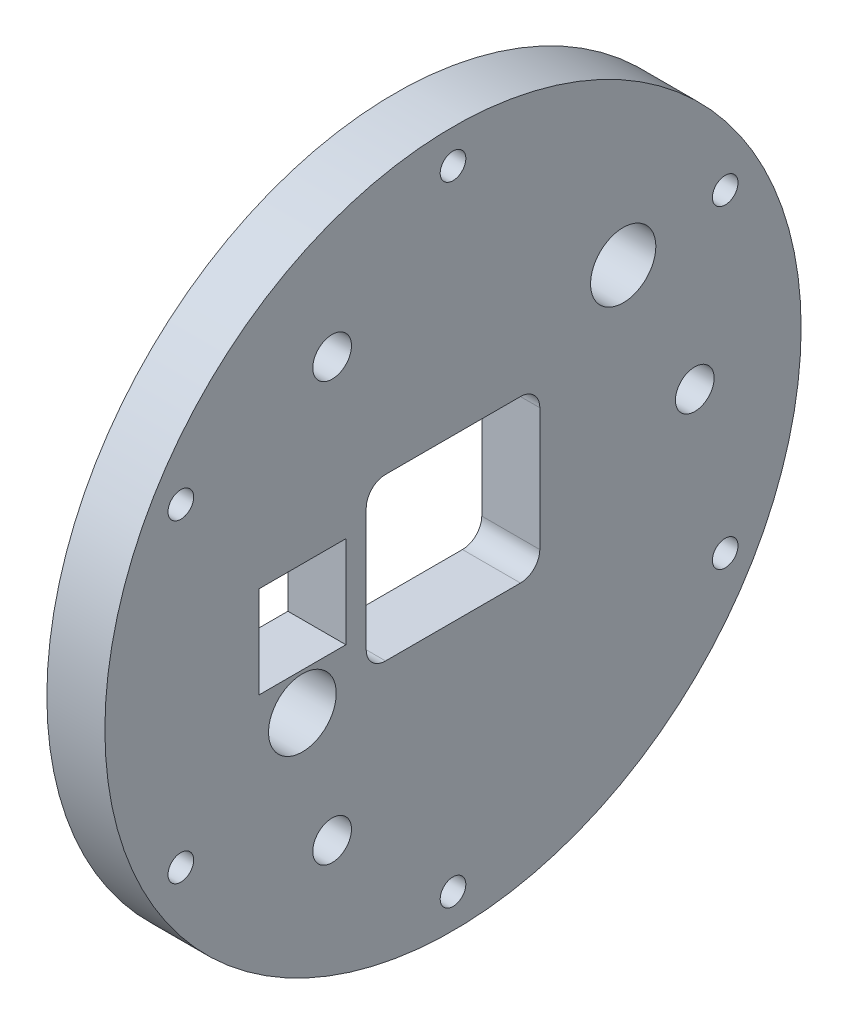
SolidWorks part; units mm, degrees
ref_plane "Front Plane" through (0, 0, 0) normal (0, 0, 1) x (1, 0, 0)
ref_plane "Top Plane" through (0, 0, 0) normal (0, 1, 0) x (1, 0, 0)
ref_plane "Right Plane" through (0, 0, 0) normal (1, 0, 0) x (0, 0, -1)
sketch "Sketch4" plane through (0, 0, 0) normal (1, 0, 0) x (0, 0, -1)
  circle A0 centre (0, 0) radius 72
  dimension "D1" = 144
sketch "Sketch2" plane through (0, 0, 0) normal (1, 0, 0) x (0, 0, -1)
  line L0 (0, 0) -> (0, 77.0354) construction
  circle A0 centre (0, 0) radius 65 construction
  circle A1 centre (0, 65) radius 2.65
  circle A2 centre (56.2917, 32.5) radius 2.65
  circle A3 centre (56.2917, -32.5) radius 2.65
  circle A4 centre (0, -65) radius 2.65
  circle A5 centre (-56.2917, -32.5) radius 2.65
  circle A6 centre (-56.2917, 32.5) radius 2.65
  point P17 (0, 0)
  dimension "D3" = 5.3
  dimension "D1" = 65
  dimension "D2" = 6
sketch "Sketch3" plane through (0, 0, 0) normal (1, 0, 0) x (0, 0, -1)
  line L0 (-4.7792, 0) -> (94.0848, 0) construction
  circle A2 centre (50, 0) radius 4
  circle A3 centre (-25, -43.3013) radius 4
  circle A4 centre (-25, 43.3013) radius 4
  dimension "D1" = 50
  dimension "D3" = 8
  dimension "D5" = 3
extrude "Boss-Extrude3" add sketch "Sketch4" along normal blind 12
extrude "Cut-Extrude6" cut sketch "Sketch3" along normal through all
extrude "Cut-Extrude1" cut sketch "Sketch2" along normal through all
sketch "Sketch1" plane through (0, 0, 0) normal (1, 0, 0) x (0, 0, -1)
  line L0 (-72, 0) -> (72, 0) construction
  line L1 (-13.95, 16.7) -> (13.95, 16.7)
  line L2 (-17.95, 12.7) -> (-17.95, -12.7)
  line L3 (-13.95, -16.7) -> (13.95, -16.7)
  line L4 (17.95, 12.7) -> (17.95, -12.7)
  line L5 (72.7609, -17.4) -> (-66.8201, -17.4) construction
  line L6 (-31.15, -17.4) -> (-31.15, 22.2578) construction
  line L7 (-40.15, 9.3) -> (-22.15, 9.3)
  line L8 (-40.15, 9.3) -> (-40.15, -9.7)
  line L9 (-40.15, -9.7) -> (-22.15, -9.7)
  line L10 (-22.15, 9.3) -> (-22.15, -9.7)
  line L11 (0, 8.4141) -> (0, -10.5859) construction
  line L12 (0, 0) -> (-23.1273, 0) construction
  circle A1 centre (-31.15, -17.4) radius 7
  arc A5 (-13.95, -16.7) -> (-17.95, -12.7) centre (-13.95, -12.7) cw
  arc A6 (13.95, -16.7) -> (17.95, -12.7) centre (13.95, -12.7) ccw
  arc A7 (17.95, 12.7) -> (13.95, 16.7) centre (13.95, 12.7) ccw
  arc A8 (-13.95, 16.7) -> (-17.95, 12.7) centre (-13.95, 12.7) ccw
  point P13 (-13.95, 16.7)
  point P29 (-17.95, -16.7)
  point P32 (17.95, -16.7)
  point P35 (17.95, 16.7)
  point P38 (-17.95, 16.7)
  dimension "D2" = 35.9
  dimension "D7" = 14
  dimension "D12" = 4
  dimension "D6" = 33.4
  dimension "D8" = 13.2
  dimension "D9" = 18
  dimension "D10" = 19
  dimension "D11" = 7.7
  dimension "D13" = 0.7
extrude "gopro" cut sketch "Sketch1" along normal through all
hole_wizard "Dégagement M121" positions "Esquisse1" profile "Esquisse2" hole size "M12" standard "DIN" end condition through all
sketch "Esquisse1" plane through (12, 0, 0) normal (1, 0, 0) x (0, 0, -1)
  point P0 (35.1983, 29.6156)
  dimension "D1" = 46
sketch "Esquisse2" plane through (12, 29.6156, -35.1983) normal (0, 1, 0) x (0, 0, -1)
  line L0 (0, 0) -> (0, 12)
  line L1 (0, 12) -> (6.75, 12)
  line L2 (6.75, 12) -> (6.75, 0)
  line L5 (6.75, 0) -> (0, 0)
  line L11 (0, -6.35) -> (0, 107.95) construction
  dimension "Diamètre du perçage jusqu'au prochain" = 13.5
  dimension "Profondeur du perçage jusqu'au prochain" = 12
